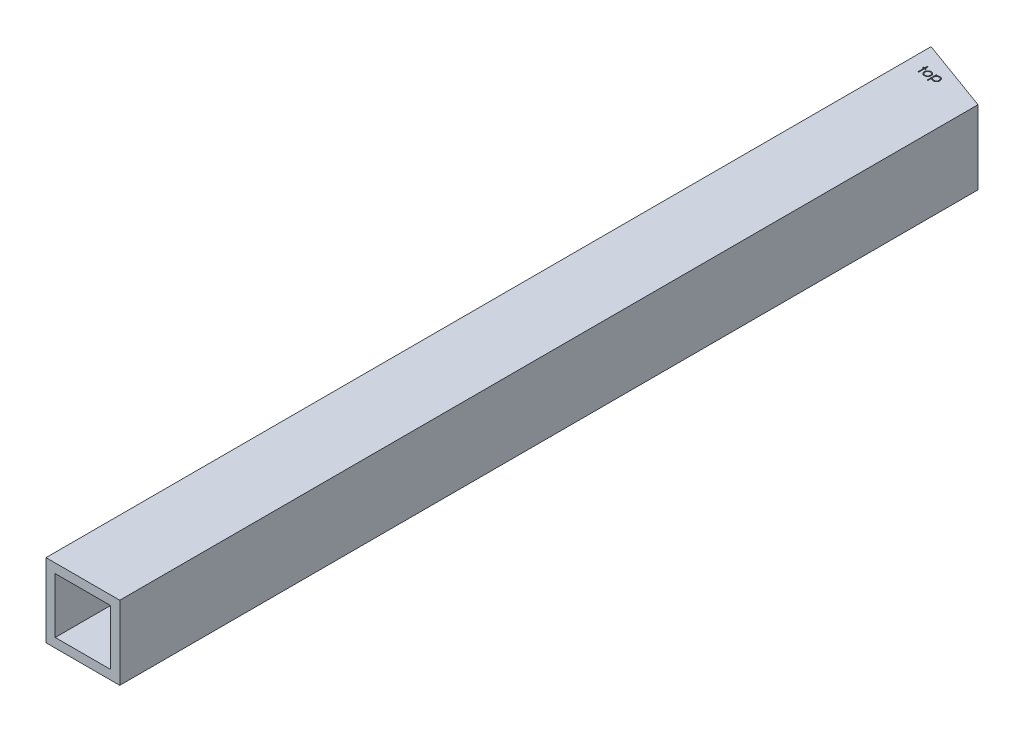
SolidWorks part; units mm, degrees
ref_plane "Front Plane" through (0, 0, 0) normal (0, 0, 1) x (1, 0, 0)
ref_plane "Top Plane" through (0, 0, 0) normal (0, 1, 0) x (1, 0, 0)
ref_plane "Right Plane" through (0, 0, 0) normal (1, 0, 0) x (0, 0, -1)
sketch "Sketch2" plane through (0, 0, 0) normal (0, 0, 1) x (1, 0, 0)
  line L1 (0, 0) -> (25.4, 0)
  line L2 (0, 0) -> (0, 25.4)
  line L3 (0, 25.4) -> (25.4, 25.4)
  line L4 (25.4, 0) -> (25.4, 25.4)
  line L5 (3.175, 22.225) -> (22.225, 22.225)
  line L6 (3.175, 22.225) -> (3.175, 3.175)
  line L7 (3.175, 3.175) -> (22.225, 3.175)
  line L8 (22.225, 22.225) -> (22.225, 3.175)
  dimension "D1" = 25.4
  dimension "D2" = 25.4
  dimension "D3" = 3.175
  dimension "D4" = 3.175
  dimension "D5" = 3.175
  dimension "D6" = 3.175
extrude "Boss-Extrude1" add sketch "Sketch2" along normal blind 304.8
sketch "Sketch3" plane through (0, 25.4, 0) normal (0, 1, 0) x (1, 0, 0)
  line L0 (0, 0) -> (25.4, -9.2448)
  line L1 (25.4, -304.8) -> (25.4, 0) construction
  line L2 (25.4, -9.2448) -> (25.4, 0)
  line L3 (25.4, 0) -> (0, 0)
  text T0 "top\r\n"
  dimension "D1" = 70
extrude "Cut-Extrude1" cut sketch "Sketch3" against normal through all
